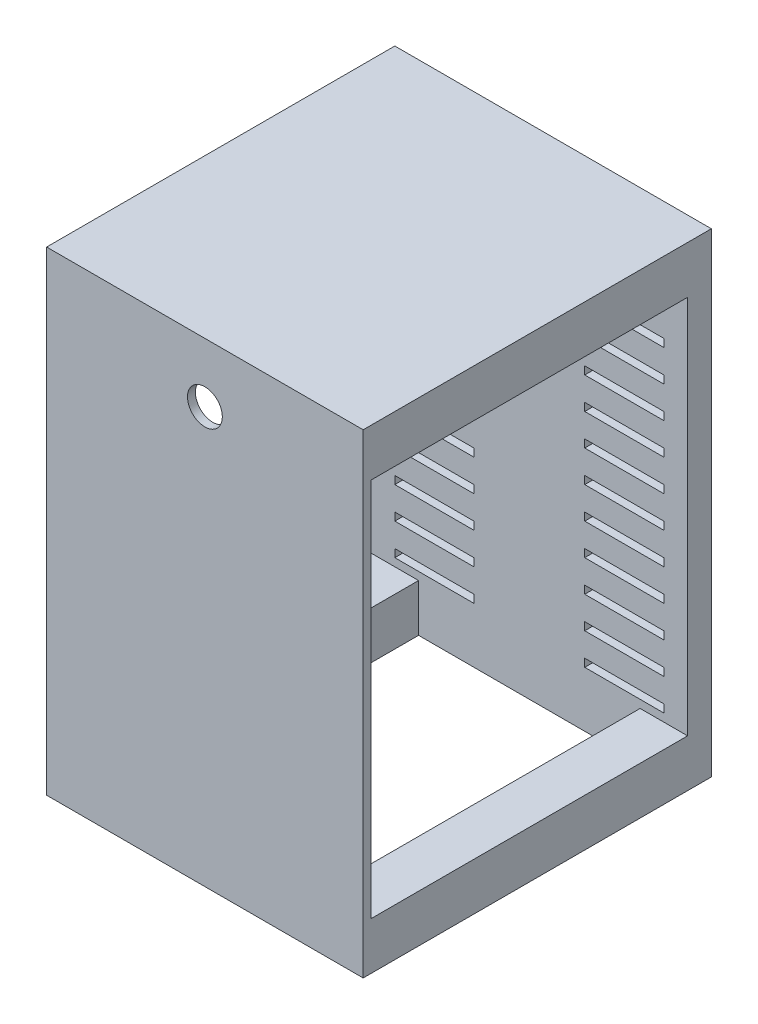
SolidWorks part; units mm, degrees
ref_plane "Alzado" through (0, 0, 0) normal (0, 0, 1) x (1, 0, 0)
ref_plane "Planta" through (0, 0, 0) normal (0, 1, 0) x (1, 0, 0)
ref_plane "Vista lateral" through (0, 0, 0) normal (1, 0, 0) x (0, 0, -1)
sketch "Croquis1" plane through (0, 0, 0) normal (0, 0, 1) x (1, 0, 0)
  line L1 (-100, -150) -> (100, -150)
  line L2 (-100, -150) -> (-100, 150)
  line L3 (-100, 150) -> (100, 150)
  line L4 (100, -150) -> (100, 150)
  line L5 (-100, -150) -> (100, 150) construction
  line L6 (-100, 150) -> (100, -150) construction
  point P0 (0, 0)
  dimension "D1" = 200
  dimension "D2" = 300
extrude "Saliente-Extruir2" add sketch "Croquis1" along normal blind 15 contours L3 L4 L1 L2
sketch "Croquis2" plane through (0, 0, 15) normal (0, 0, 1) x (1, 0, 0)
  line L1 (-100, 150) -> (-70, 150)
  line L2 (-100, 150) -> (-100, 120)
  line L3 (-100, 120) -> (-70, 120)
  line L4 (-70, 150) -> (-70, 120)
  line L5 (100, 150) -> (70, 150)
  line L6 (100, 150) -> (100, 120)
  line L7 (100, 120) -> (70, 120)
  line L8 (70, 150) -> (70, 120)
  line L9 (-100, -150) -> (-70, -150)
  line L10 (-100, -150) -> (-100, -120)
  line L11 (-100, -120) -> (-70, -120)
  line L12 (-70, -150) -> (-70, -120)
  line L13 (100, -150) -> (70, -150)
  line L14 (100, -150) -> (100, -120)
  line L15 (100, -120) -> (70, -120)
  line L16 (70, -150) -> (70, -120)
  dimension "D1" = 30
  dimension "D2" = 30
extrude "Saliente-Extruir3" add sketch "Croquis2" along normal blind 200
sketch "Croquis3" plane through (0, 0, 215) normal (0, 0, 1) x (1, 0, 0)
  line L1 (-100, 150) -> (100, 150)
  line L2 (-100, 150) -> (-100, -150)
  line L3 (-100, -150) -> (100, -150)
  line L4 (100, 150) -> (100, -150)
extrude "Saliente-Extruir4" add sketch "Croquis3" along normal blind 5
sketch "Croquis7" plane through (0, 0, 0) normal (0, 0, -1) x (-1, 0, 0)
  line L0 (35, 110) -> (85, 110)
  line L1 (-85, 110) -> (-35, 110)
  line L2 (-85, 110) -> (-85, 105)
  line L3 (-85, 105) -> (-35, 105)
  line L4 (-35, 110) -> (-35, 105)
  line L5 (85, 110) -> (85, 105)
  line L6 (35, 105) -> (85, 105)
  line L7 (35, 110) -> (35, 105)
  line L8 (35, 90) -> (85, 90)
  line L9 (85, 90) -> (85, 85)
  line L10 (35, 85) -> (85, 85)
  line L11 (35, 90) -> (35, 85)
  line L12 (35, 70) -> (85, 70)
  line L13 (85, 70) -> (85, 65)
  line L14 (35, 65) -> (85, 65)
  line L15 (35, 70) -> (35, 65)
  line L16 (35, 50) -> (85, 50)
  line L17 (85, 50) -> (85, 45)
  line L18 (35, 45) -> (85, 45)
  line L19 (35, 50) -> (35, 45)
  line L20 (35, 30) -> (85, 30)
  line L21 (85, 30) -> (85, 25)
  line L22 (35, 25) -> (85, 25)
  line L23 (35, 30) -> (35, 25)
  line L24 (35, 10) -> (85, 10)
  line L25 (85, 10) -> (85, 5)
  line L26 (35, 5) -> (85, 5)
  line L27 (35, 10) -> (35, 5)
  line L28 (35, -10) -> (85, -10)
  line L29 (85, -10) -> (85, -15)
  line L30 (35, -15) -> (85, -15)
  line L31 (35, -10) -> (35, -15)
  line L32 (35, -30) -> (85, -30)
  line L33 (85, -30) -> (85, -35)
  line L34 (35, -35) -> (85, -35)
  line L35 (35, -30) -> (35, -35)
  line L36 (35, -50) -> (85, -50)
  line L37 (85, -50) -> (85, -55)
  line L38 (35, -55) -> (85, -55)
  line L39 (35, -50) -> (35, -55)
  line L40 (35, -70) -> (85, -70)
  line L41 (85, -70) -> (85, -75)
  line L42 (35, -75) -> (85, -75)
  line L43 (35, -70) -> (35, -75)
  line L64 (-85, 90) -> (-35, 90)
  line L65 (-35, 90) -> (-35, 85)
  line L66 (-85, 85) -> (-35, 85)
  line L67 (-85, 90) -> (-85, 85)
  line L68 (-85, 70) -> (-35, 70)
  line L69 (-35, 70) -> (-35, 65)
  line L70 (-85, 65) -> (-35, 65)
  line L71 (-85, 70) -> (-85, 65)
  line L72 (-85, 50) -> (-35, 50)
  line L73 (-35, 50) -> (-35, 45)
  line L74 (-85, 45) -> (-35, 45)
  line L75 (-85, 50) -> (-85, 45)
  line L76 (-85, 30) -> (-35, 30)
  line L77 (-35, 30) -> (-35, 25)
  line L78 (-85, 25) -> (-35, 25)
  line L79 (-85, 30) -> (-85, 25)
  line L80 (-85, 10) -> (-35, 10)
  line L81 (-35, 10) -> (-35, 5)
  line L82 (-85, 5) -> (-35, 5)
  line L83 (-85, 10) -> (-85, 5)
  line L84 (-85, -10) -> (-35, -10)
  line L85 (-35, -10) -> (-35, -15)
  line L86 (-85, -15) -> (-35, -15)
  line L87 (-85, -10) -> (-85, -15)
  line L88 (-85, -30) -> (-35, -30)
  line L89 (-35, -30) -> (-35, -35)
  line L90 (-85, -35) -> (-35, -35)
  line L91 (-85, -30) -> (-85, -35)
  line L92 (-85, -50) -> (-35, -50)
  line L93 (-35, -50) -> (-35, -55)
  line L94 (-85, -55) -> (-35, -55)
  line L95 (-85, -50) -> (-85, -55)
  line L96 (-85, -70) -> (-35, -70)
  line L97 (-35, -70) -> (-35, -75)
  line L98 (-85, -75) -> (-35, -75)
  line L99 (-85, -70) -> (-85, -75)
  line L120 (-85, -90) -> (-35, -90)
  line L121 (-35, -90) -> (-35, -95)
  line L122 (-85, -95) -> (-35, -95)
  line L123 (-85, -90) -> (-85, -95)
  line L124 (35, -90) -> (85, -90)
  line L125 (85, -90) -> (85, -95)
  line L126 (35, -95) -> (85, -95)
  line L127 (35, -90) -> (35, -95)
  line L128 (-85, -110) -> (-35, -110)
  line L129 (-35, -110) -> (-35, -115)
  line L130 (-85, -115) -> (-35, -115)
  line L131 (-85, -110) -> (-85, -115)
  line L132 (35, -110) -> (85, -110)
  line L133 (85, -110) -> (85, -115)
  line L134 (35, -115) -> (85, -115)
  line L135 (35, -110) -> (35, -115)
  line L152 (-85, 110) -> (-85, 150) construction
  line L153 (100, 150) -> (-100, 150) construction
  line L154 (-85, 110) -> (-100, 110) construction
  line L155 (-100, -150) -> (-100, 150) construction
  line L156 (-85, 105) -> (-100, 105) construction
  line L157 (85, 110) -> (100, 110) construction
  line L158 (100, -150) -> (100, 150) construction
  line L159 (-85, -130) -> (-35, -130) [skipped]
  line L160 (-35, -130) -> (-35, -135) [skipped]
  line L161 (-85, -135) -> (-35, -135) [skipped]
  line L162 (-85, -130) -> (-85, -135) [skipped]
  line L219 (-85, -150) -> (-35, -150) [skipped]
  line L220 (-35, -150) -> (-35, -155) [skipped]
  line L221 (-85, -155) -> (-35, -155) [skipped]
  line L222 (-85, -150) -> (-85, -155) [skipped]
  line L223 (35, -150) -> (85, -150) [skipped]
  line L224 (85, -150) -> (85, -155) [skipped]
  line L225 (35, -155) -> (85, -155) [skipped]
  line L226 (35, -150) -> (35, -155) [skipped]
  line L227 (35, -130) -> (85, -130) [skipped]
  line L228 (85, -130) -> (85, -135) [skipped]
  line L229 (35, -135) -> (85, -135) [skipped]
  line L230 (35, -130) -> (35, -135) [skipped]
  point P60 (0, 0)
  dimension "D1" = 5
  dimension "D2" = 50
  dimension "D5" = 40
  dimension "D3" = 2
  dimension "D4" = 14
extrude "Cortar-Extruir1" cut sketch "Croquis7" against normal blind 20
sketch "Croquis9" plane through (0, 150, 0) normal (0, 1, 0) x (1, 0, 0)
  line L1 (100, -220) -> (-100, -220)
  line L2 (100, -220) -> (100, 0)
  line L3 (100, 0) -> (-100, 0)
  line L4 (-100, -220) -> (-100, 0)
extrude "Saliente-Extruir6" add sketch "Croquis9" against normal blind 5
sketch "Croquis11" plane through (0, 0, 220) normal (0, 0, 1) x (1, 0, 0)
  circle A0 centre (0, 112.5528) radius 11
  dimension "D1" = 22
extrude "Cortar-Extruir3" cut sketch "Croquis11" against normal blind 10
